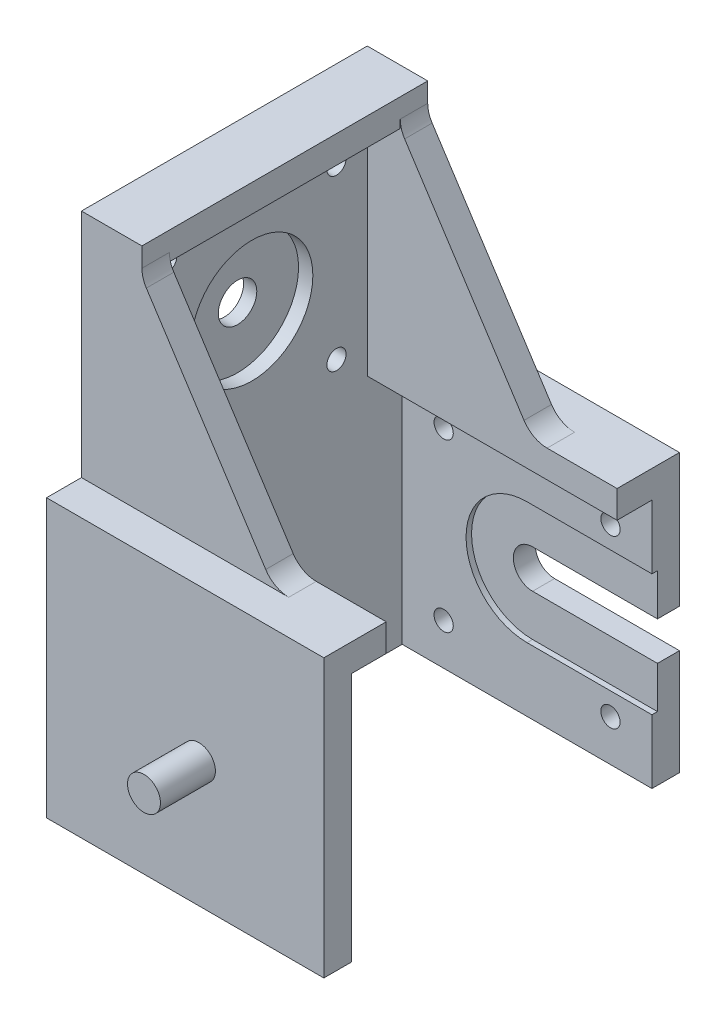
SolidWorks part; units mm, degrees
ref_plane "Front Plane" through (0, 0, 0) normal (0, 0, 1) x (1, 0, 0)
ref_plane "Top Plane" through (0, 0, 0) normal (0, 1, 0) x (1, 0, 0)
ref_plane "Right Plane" through (0, 0, 0) normal (1, 0, 0) x (0, 0, -1)
sketch "Sketch1" plane through (0, 0, 0) normal (0, 1, 0) x (1, 0, 0)
  line L0 (22.725, 27.35) -> (22.725, 32.35)
  line L1 (22.725, 32.35) -> (-22.725, 32.35)
  line L2 (0, 27.35) -> (22.725, 27.35)
  line L4 (22.725, -27.35) -> (-22.725, -27.35)
  line L5 (-22.725, -27.35) -> (-22.725, 27.35)
  line L6 (-22.725, 27.35) -> (0, 27.35)
  line L7 (-22.725, 32.35) -> (-27.725, 32.35)
  line L8 (-27.725, 32.35) -> (-27.725, -27.35)
  line L9 (-27.725, -27.35) -> (-27.725, -32.35)
  line L10 (-27.725, -32.35) -> (22.725, -32.35)
  line L11 (22.725, -32.35) -> (22.725, -27.35)
  dimension "D1" = 54.7
  dimension "D2" = 5
  dimension "D3" = 22.725
  dimension "D4" = 45.45
  dimension "D5" = 5
  dimension "D6" = 5
extrude "Boss-Extrude1" add sketch "Sketch1" along normal blind 45.45
sketch "Sketch5" plane through (0, 0, -27.35) normal (0, 0, 1) x (1, 0, 0)
  line L0 (-22.725, 22.725) -> (22.725, 22.725)
  line L1 (-22.725, 45.45) -> (-22.725, 0) construction
  line L2 (22.725, 45.45) -> (22.725, 0) construction
  line L3 (0, 33.825) -> (22.725, 33.825)
  line L4 (22.725, 45.45) -> (22.725, 0) construction
  line L5 (22.725, 33.825) -> (22.725, 11.625)
  line L6 (22.725, 11.625) -> (0, 11.625)
  arc A0 (0, 33.825) -> (0, 11.625) centre (0, 22.725) ccw
  dimension "D1" = 22.2
extrude "Cut-Extrude4" cut sketch "Sketch5" against normal blind 1 contours L3 L5 L6 A0
sketch "Sketch6" plane through (0, 0, -27.35) normal (0, 0, 1) x (1, 0, 0)
  line L0 (0, 26.225) -> (22.725, 26.225)
  line L1 (22.725, 33.825) -> (22.725, 11.625) construction
  line L2 (22.725, 26.225) -> (22.725, 19.225)
  line L3 (22.725, 19.225) -> (0, 19.225)
  arc A0 (0, 26.225) -> (0, 19.225) centre (0, 22.725) ccw
  dimension "D1" = 7
extrude "Cut-Extrude5" cut sketch "Sketch6" against normal up to surface (5 mm away) up to face at (-2.5, 22.725, -32.35)
sketch "Sketch9" plane through (0, 0, -27.35) normal (0, 0, 1) x (1, 0, 0)
  line L0 (-22.725, 45.45) -> (22.725, 45.45) construction
  line L1 (22.725, 45.45) -> (22.725, 33.825) construction
  line L2 (-22.725, 45.45) -> (-22.725, 0) construction
  line L3 (-22.725, 0) -> (22.725, 0) construction
  line L4 (22.725, 11.625) -> (22.725, 0) construction
  circle A0 centre (15.175, 37.9) radius 1.75
  circle A1 centre (-15.175, 37.9) radius 1.75
  circle A2 centre (15.175, 7.55) radius 1.75
  circle A3 centre (-15.175, 7.55) radius 1.75
  dimension "D1" = 3.5
  dimension "D2" = 1.75
  dimension "D3" = 1.75
  dimension "D4" = 1.75
  dimension "D5" = 7.55
  dimension "D6" = 7.55
  dimension "D7" = 7.55
  dimension "D8" = 7.55
  dimension "D9" = 7.55
  dimension "D10" = 7.55
  dimension "D11" = 7.55
  dimension "D12" = 7.55
extrude "Cut-Extrude6" cut sketch "Sketch9" against normal up to surface (5 mm away) up to face at (3.9938, 22.725, -32.35)
sketch "Sketch10" plane through (-22.725, 0, 0) normal (1, 0, 0) x (0, 0, -1)
  line L0 (0, 45.45) -> (21, 45.45)
  line L1 (-27.35, 45.45) -> (27.35, 45.45) construction
  line L2 (0, 45.45) -> (-21, 45.45)
  line L3 (-21, 45.45) -> (-21, 87.45)
  line L4 (-21, 87.45) -> (21, 87.45)
  line L5 (21, 87.45) -> (21, 45.45)
  dimension "D1" = 21
  dimension "D2" = 21
  dimension "D3" = 42
  dimension "D4" = 42
extrude "Boss-Extrude2" add sketch "Sketch10" against normal blind 5
sketch "Sketch11" plane through (-22.725, 0, 0) normal (1, 0, 0) x (0, 0, -1)
  line L0 (-21, 45.45) -> (21, 45.45)
  line L1 (21, 45.45) -> (21, 87.45) construction
  line L2 (-21, 87.45) -> (-21, 45.45) construction
  line L3 (21, 87.45) -> (-21, 87.45) construction
  circle A0 centre (-15.4, 81.65) radius 1.75
  circle A1 centre (15.4, 81.65) radius 1.75
  circle A2 centre (-15.4, 50.85) radius 1.715
  circle A3 centre (15.4, 50.85) radius 1.75
  dimension "D1" = 3.5
  dimension "D2" = 3.5
  dimension "D3" = 3.43
  dimension "D4" = 1.75
  dimension "D5" = 5.4
  dimension "D6" = 5.4
  dimension "D7" = 5.6
  dimension "D8" = 5.6
  dimension "D9" = 5.6
  dimension "D10" = 5.6
  dimension "D11" = 5.8
  dimension "D12" = 5.8
extrude "Cut-Extrude7" cut sketch "Sketch11" against normal up to surface (5 mm away) contours A2 | A3 | A0 | A1 up to face at (-27.725, 44.5875, 0)
sketch "Sketch13" plane through (-22.725, 0, 0) normal (1, 0, 0) x (0, 0, -1)
  line L0 (0, 87.45) -> (0, 66.25)
  line L1 (21, 87.45) -> (-21, 87.45) construction
  circle A0 centre (0, 66.25) radius 3.5
  circle A1 centre (0, 66.25) radius 11.1
  dimension "D2" = 7
  dimension "D3" = 22.2
  dimension "D1" = 21.2
extrude "Cut-Extrude8" cut sketch "Sketch13" against normal up to surface (5 mm away) contours A0 up to face at (-27.725, 50.85, -17.15)
extrude "Cut-Extrude9" cut sketch "Sketch13<3>" against normal blind 2.6 contours A1
sketch "Sketch13<3>" plane through (-22.725, 0, 0) normal (1, 0, 0) x (0, 0, -1) same geometry as "Sketch13"
sketch "Sketch14" plane through (0, 45.45, 0) normal (0, 1, 0) x (1, 0, 0)
  line L0 (-27.725, 21) -> (-27.725, 32.35)
  line L1 (-27.725, 32.35) -> (22.725, 32.35)
  line L2 (-27.725, 21) -> (22.725, 21)
  line L3 (22.725, 21) -> (22.725, 32.35)
extrude "Boss-Extrude3" add sketch "Sketch14" along normal blind 5
sketch "Sketch15" plane through (0, 45.45, 0) normal (0, 1, 0) x (1, 0, 0)
  line L0 (-27.725, -21) -> (-27.725, -32.35)
  line L1 (-27.725, -32.35) -> (22.725, -32.35)
  line L2 (-27.725, -21) -> (22.725, -21)
  line L3 (22.725, -21) -> (22.725, -32.35)
extrude "Boss-Extrude4" add sketch "Sketch15" along normal blind 5
sketch "Sketch17" plane through (-27.725, 0, 0) normal (-1, 0, 0) x (0, 0, 1)
  line L0 (21, 87.45) -> (21, 92.45)
  line L1 (21, 92.45) -> (-21, 92.45)
  line L2 (-21, 92.45) -> (-21, 87.45)
  line L3 (-21, 87.45) -> (21, 87.45)
  dimension "D1" = 5
extrude "Boss-Extrude5" add sketch "Sketch17" against normal blind 11
sketch "Sketch19" plane through (0, 0, 21) normal (0, 0, 1) x (1, 0, 0)
  line L0 (-22.725, 50.45) -> (7.275, 50.45)
  line L1 (7.275, 50.45) -> (-16.725, 87.45)
  line L2 (-16.725, 87.45) -> (-16.725, 92.45)
  line L3 (-16.725, 92.45) -> (-27.725, 92.45) construction
  line L4 (-16.725, 87.45) -> (-16.725, 92.45) construction
  line L5 (-16.725, 92.45) -> (-27.725, 92.45)
  line L6 (-27.725, 92.45) -> (-27.725, 50.45)
  line L7 (-27.725, 50.45) -> (-22.725, 50.45)
  dimension "D1" = 30
extrude "Boss-Extrude6" add sketch "Sketch19" along normal blind 5
sketch "Sketch20" plane through (0, 0, -21) normal (0, 0, -1) x (-1, 0, 0)
  line L0 (22.725, 50.45) -> (-7.275, 50.45)
  line L1 (22.725, 50.45) -> (-22.725, 50.45) construction
  line L2 (-7.275, 50.45) -> (16.725, 87.45)
  line L3 (16.725, 87.45) -> (16.725, 92.45)
  line L4 (16.725, 92.45) -> (27.725, 92.45)
  line L5 (27.725, 92.45) -> (27.725, 50.45)
  line L6 (27.725, 50.45) -> (22.725, 50.45)
  dimension "D1" = 30
extrude "Boss-Extrude7" add sketch "Sketch20" along normal blind 5
sketch "Sketch21" plane through (0, 0, 27.35) normal (0, 0, -1) x (-1, 0, 0)
  line L0 (-22.725, 22.725) -> (22.725, 22.725)
  line L1 (-22.725, 45.45) -> (-22.725, 0) construction
  line L2 (22.725, 45.45) -> (22.725, 0) construction
  circle A0 centre (0, 22.725) radius 3
  dimension "D1" = 6
extrude "Boss-Extrude8" add sketch "Sketch21" against normal blind 15 contours A0
ref_plane "Plane1" through (7.275, 50.45, -21) normal (0, 0, 1) x (1, 0, 0)
fillet "Fillet1" radius 5 2 edges at (7.275, 50.45, -23.5) (7.275, 50.45, 23.5)
fillet "Fillet2" radius 5 2 edges at (-16.725, 87.45, -23.5) (-16.725, 87.45, 23.5)
